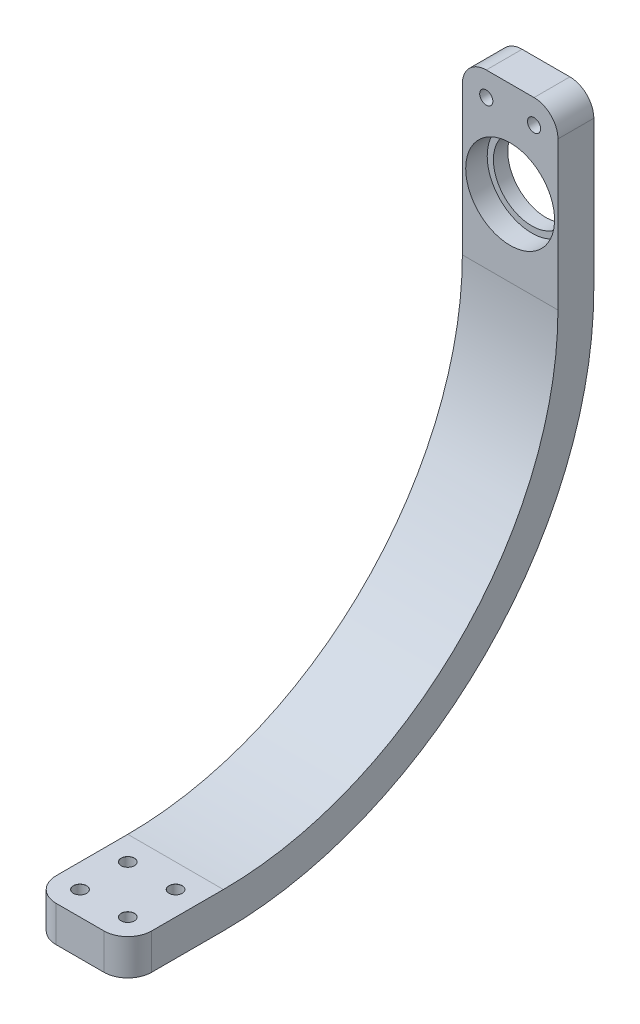
SolidWorks part; units mm, degrees
ref_plane "Front Plane" through (0, 0, 0) normal (0, 0, 1) x (1, 0, 0)
ref_plane "Top Plane" through (0, 0, 0) normal (0, 1, 0) x (1, 0, 0)
ref_plane "Right Plane" through (0, 0, 0) normal (1, 0, 0) x (0, 0, -1)
sketch "Sketch6" plane through (0, 0, 0) normal (1, 0, 0) x (0, 0, -1)
  line L0 (0, 0) -> (40, 0)
  line L1 (0, 0) -> (0, 15)
  line L2 (0, 15) -> (40, 15)
  line L3 (180, 155) -> (180, 227)
  line L4 (180, 227) -> (195, 227)
  line L5 (195, 227) -> (195, 155)
  arc A0 (40, 15) -> (180, 155) centre (40, 155) ccw
  arc A1 (40, 0) -> (195, 155) centre (40, 155) ccw
  dimension "D3" = 195
  dimension "D1" = 15
  dimension "D2" = 40
  dimension "D4" = 227
extrude "Boss-Extrude2" add sketch "Sketch6" along normal blind 40
sketch "Sketch9" plane through (0, 15, 0) normal (0, 1, 0) x (1, 0, 0)
  line L0 (10, 30) -> (30, 30) construction
  line L1 (30, 30) -> (30, 10) construction
  line L2 (30, 10) -> (10, 10) construction
  line L3 (10, 10) -> (10, 30) construction
  line L5 (40, 0) -> (0, 0) construction
  line L6 (40, 40) -> (40, 0) construction
  point P0 (10, 30)
  point P2 (30, 30)
  point P4 (10, 10)
  point P6 (30, 10)
  point P21 (20, 0)
  point P22 (20, 10)
  point P25 (40, 20)
  point P26 (30, 20)
  dimension "D1" = 20
hole_wizard "M5 Clearance Hole2" positions "Sketch9" profile "Sketch8" hole size "M5" standard "ANSI Metric" end condition through all
sketch "Sketch8" plane through (10, 15, -30) normal (1, 0, 0) x (0, 0, 1)
  line L0 (0, 0) -> (0, 15)
  line L1 (0, 15) -> (2.75, 15)
  line L2 (2.75, 15) -> (2.75, 0.025)
  line L3 (2.75, 0.025) -> (2.775, 0)
  line L5 (2.775, 0) -> (0, 0)
  line L6 (-2.75, 0.025) -> (-2.775, 0) construction
  line L11 (0, -6.35) -> (0, 107.95) construction
  dimension "Thru Hole Dia." = 5.5
  dimension "Thru Hole Depth" = 15
  dimension "Near C'Sink Dia." = 5.55
  dimension "Near C'Sink Angle" = 90
sketch "Sketch10" plane through (0, 0, -195) normal (0, 0, -1) x (-1, 0, 0)
  line L0 (-40, 227) -> (0, 227) construction
  circle A0 centre (-20, 187) radius 16
  point P4 (-20, 227)
  dimension "D1" = 32
  dimension "D2" = 40
extrude "Cut-Extrude1" cut sketch "Sketch10" against normal up to next
sketch "Sketch11" plane through (0, 0, -180) normal (0, 0, -1) x (-1, 0, 0)
  circle A0 centre (-20, 187) radius 18.6
  dimension "D1" = 37.2
extrude "Cut-Extrude2" cut sketch "Sketch11" along normal blind 9
fillet "Fillet1" radius 10 4 edges at (40, 7.5, 0) (0, 7.5, 0) (40, 227, -187.5) (0, 227, -187.5) first distance on face at (40, 91.6129, -111.3871) first distance on face at (0, 91.6129, -111.3871)
sketch "Sketch14" plane through (0, 0, -195) normal (0, 0, -1) x (-1, 0, 0)
  line L0 (-30, 217) -> (-10, 217) construction
  line L2 (-30, 227) -> (-10, 227) construction
  circle A0 centre (-20, 187) radius 16 construction
  point P0 (-30, 217)
  point P2 (-10, 217)
  point P12 (-20, 227)
  point P13 (-20, 217)
  dimension "D2" = 30
  dimension "D1" = 20
hole_wizard "M5 Clearance Hole3" positions "Sketch14" profile "Sketch13" hole size "M5" standard "ANSI Metric" end condition through all
sketch "Sketch13" plane through (30, 217, -195) normal (1, 0, 0) x (0, 1, 0)
  line L0 (0, 0) -> (0, 195.5637)
  line L1 (0, 195.5637) -> (2.75, 195.5637)
  line L2 (2.75, 195.5637) -> (2.75, 0.025)
  line L3 (2.75, 0.025) -> (2.775, 0)
  line L5 (2.775, 0) -> (0, 0)
  line L6 (-2.75, 0.025) -> (-2.775, 0) construction
  line L11 (0, -6.35) -> (0, 107.95) construction
  dimension "Thru Hole Dia." = 5.5
  dimension "Thru Hole Depth" = 195.5637
  dimension "Near C'Sink Dia." = 5.55
  dimension "Near C'Sink Angle" = 90
